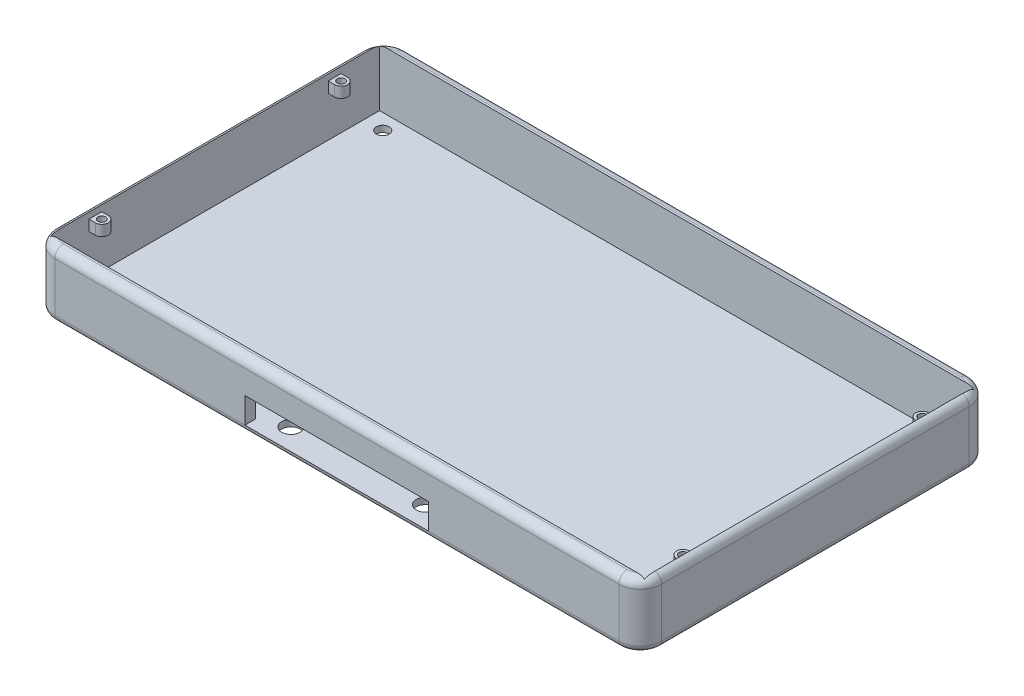
SolidWorks part; units mm, degrees
ref_plane "前视基准面" through (0, 0, 0) normal (0, 0, 1) x (1, 0, 0)
ref_plane "上视基准面" through (0, 0, 0) normal (0, 1, 0) x (1, 0, 0)
ref_plane "右视基准面" through (0, 0, 0) normal (1, 0, 0) x (0, 0, -1)
sketch "草图1" plane through (0, 0, 0) normal (0, 1, 0) x (1, 0, 0)
  line L1 (0, 0) -> (142, 0)
  line L2 (0, 0) -> (0, -82)
  line L3 (0, -82) -> (142, -82)
  line L4 (142, 0) -> (142, -82)
  dimension "D1" = 142
  dimension "D2" = 82
extrude "凸台-拉伸1" add sketch "草图1" along normal blind 15 contours L1 L4 L3 L2
shell "抽壳1" thickness 1.5 removed face at (71, 15, 41)
sketch "草图2" plane through (0, 1.5, 0) normal (0, 1, 0) x (1, 0, 0)
  line L0 (55.25, -77) -> (1.5, -77) construction
  line L1 (1.5, -1.5) -> (1.5, -80.5) construction
  line L2 (86.75, -77) -> (140.5, -77) construction
  line L3 (140.5, -1.5) -> (140.5, -80.5) construction
  line L4 (0, -82) -> (142, -82) construction
  circle A0 centre (86.75, -77) radius 2.15
  circle A1 centre (55.25, -77) radius 2.15
  dimension "D1" = 4.3
  dimension "D2" = 31.5
  dimension "5" = 5
extrude "切除-拉伸1" cut sketch "草图2" against normal blind 15
sketch "草图4" plane through (0, 1.5, 0) normal (0, 1, 0) x (1, 0, 0)
  line L0 (5.9, -75.85) -> (1.5, -75.85) construction
  line L1 (1.5, -1.5) -> (1.5, -80.5) construction
  line L2 (5.9, -75.85) -> (5.9, -1.5) construction
  line L3 (1.5, -1.5) -> (140.5, -1.5) construction
  line L4 (5.9, -6.15) -> (1.5, -6.15) construction
  line L5 (1.5, -1.5) -> (1.5, -80.5) construction
  line L6 (136.1, -75.85) -> (136.1, -1.5) construction
  line L7 (1.5, -1.5) -> (140.5, -1.5) construction
  line L8 (5.9, -6.15) -> (5.9, -80.5) construction
  line L9 (1.5, -80.5) -> (140.5, -80.5) construction
  line L10 (136.1, -6.15) -> (136.1, -80.5) construction
  line L11 (136.1, -75.85) -> (140.5, -75.85) construction
  line L12 (140.5, -1.5) -> (140.5, -80.5) construction
  line L13 (136.1, -6.15) -> (140.5, -6.15) construction
  circle A0 centre (5.9, -75.85) radius 1.5
  circle A1 centre (136.1, -75.85) radius 1.5
  circle A2 centre (5.9, -6.15) radius 1.5
  circle A3 centre (136.1, -6.15) radius 1.5
  dimension "D1" = 3
  dimension "D2" = 130.2
  dimension "D3" = 69.7
extrude "切除-拉伸2" cut sketch "草图4" against normal blind 15
sketch "草图5" plane through (0, 0, 82) normal (0, 0, 1) x (1, 0, 0)
  line L0 (0, 0) -> (142, 0) construction
  line L1 (49.5, 7.5) -> (92.5, 7.5)
  line L2 (49.5, 7.5) -> (49.5, 1.5)
  line L3 (49.5, 1.5) -> (92.5, 1.5)
  line L4 (92.5, 7.5) -> (92.5, 1.5)
  line L5 (49.5, 4.5) -> (0, 4.5) construction
  line L6 (0, 15) -> (0, 0) construction
  line L7 (92.5, 4.5) -> (142, 4.5) construction
  line L8 (142, 15) -> (142, 0) construction
  dimension "D1" = 43
  dimension "D2" = 6
  dimension "D3" = 1.5
extrude "切除-拉伸3" cut sketch "草图5" against normal blind 15
ref_plane "基准面4" through (0, 11, 0) normal (0, 1, 0) x (1, 0, 0)
sketch "草图6" plane through (0, 11, 0) normal (0, 1, 0) x (1, 0, 0)
  line L0 (1.5, -67.5) -> (4.5, -67.5)
  line L1 (1.5, -11.5) -> (4.5, -11.5)
  line L2 (1.5, -11.5) -> (1.5, -14.5)
  line L3 (1.5, -14.5) -> (4.5, -14.5)
  line L4 (4.5, -11.5) -> (4.5, -14.5)
  line L5 (1.5, -67.5) -> (1.5, -70.5)
  line L6 (1.5, -70.5) -> (4.5, -70.5)
  line L7 (4.5, -67.5) -> (4.5, -70.5)
  line L8 (137.5, -11.5) -> (140.5, -11.5)
  line L9 (137.5, -11.5) -> (137.5, -14.5)
  line L10 (137.5, -14.5) -> (140.5, -14.5)
  line L11 (140.5, -11.5) -> (140.5, -14.5)
  line L12 (137.5, -67.5) -> (140.5, -67.5)
  line L13 (137.5, -67.5) -> (137.5, -70.5)
  line L14 (137.5, -70.5) -> (140.5, -70.5)
  line L15 (140.5, -67.5) -> (140.5, -70.5)
  line L16 (140.5, -1.5) -> (140.5, -80.5) construction
  line L18 (1.5, -1.5) -> (1.5, -80.5) construction
  line L19 (1.5, -1.5) -> (140.5, -1.5) construction
  line L20 (1.5, -80.5) -> (49.5, -80.5) construction
  dimension "D1" = 3
  dimension "D2" = 3
  dimension "D3" = 3
  dimension "D4" = 0
  dimension "D5" = 3
  dimension "D6" = 0
  dimension "D7" = 10
  dimension "D8" = 10
  dimension "D9" = 3
extrude "凸台-拉伸2" add sketch "草图6" along normal blind 2.5
sketch "草图7" plane through (0, 13.5, 0) normal (0, 1, 0) x (1, 0, 0)
  line L0 (4.5, -11.5) -> (1.5, -11.5) construction
  line L1 (1.5, -11.5) -> (1.5, -14.5) construction
  line L2 (1.5, -70.5) -> (4.5, -70.5) construction
  line L3 (140.5, -1.5) -> (140.5, -80.5) construction
  line L4 (1.5, -1.5) -> (140.5, -1.5) construction
  line L5 (92.5, -80.5) -> (140.5, -80.5) construction
  circle A0 centre (3, -13) radius 0.9
  circle A1 centre (3, -69) radius 0.9024
  circle A2 centre (139, -69) radius 0.9
  circle A3 centre (139, -13) radius 0.9
  dimension "D1" = 1.8
  dimension "D5" = 1.8048
  dimension "D7" = 1.8
  dimension "D8" = 1.8
  dimension "D2" = 1.5
  dimension "D3" = 1.5
  dimension "D4" = 1.5
  dimension "D6" = 1.5
  dimension "D9" = 11.5
  dimension "D10" = 11.5
extrude "切除-拉伸4" cut sketch "草图7" against normal up to next
fillet "圆角4" 2 edges at (4.5, 12.25, 14.5) (4.5, 12.25, 11.5) type full round first side face at (3, 12.25, 14.5) second side face at (3, 12.25, 11.5) middle face at (4.5, 12.25, 13)
fillet "圆角5" 2 edges at (4.5, 12.25, 67.5) (4.5, 12.25, 70.5) type full round first side face at (3, 12.25, 67.5) second side face at (3, 12.25, 70.5) middle face at (4.5, 12.25, 69)
fillet "圆角6" 2 edges at (137.5, 12.25, 11.5) (137.5, 12.25, 14.5) type full round first side face at (139, 12.25, 11.5) second side face at (139, 12.25, 14.5) middle face at (137.5, 12.25, 13)
fillet "圆角7" 2 edges at (137.5, 12.25, 67.5) (137.5, 12.25, 70.5) type full round first side face at (139, 12.25, 67.5) second side face at (139, 12.25, 70.5) middle face at (137.5, 12.25, 69)
fillet "圆角8" radius 5 4 edges at (0, 7.5, 82) (0, 7.5, 0) (142, 7.5, 0) (142, 7.5, 82)
fillet "圆角13" radius 1.5 8 edges at (1.4645, 0, 1.4645) (71, 0, 0) (140.5355, 0, 1.4645) (142, 0, 41) (140.5355, 0, 80.5355) (71, 0, 82) (1.4645, 0, 80.5355) (0, 0, 41)
sketch "草图8" plane through (0, 15, 0) normal (0, 1, 0) x (1, 0, 0)
  line L0 (1.5, -1.5) -> (140.5, -1.5) construction
  line L1 (1.5, -1.5) -> (140.5, -1.5)
  line L2 (1.5, -1.5) -> (1.5, -2.5)
  line L3 (1.5, -2.5) -> (140.5, -2.5)
  line L4 (140.5, -1.5) -> (140.5, -2.5)
  line L5 (1.5, -1.5) -> (1.5, -80.5) construction
  line L6 (140.5, -1.5) -> (140.5, -80.5) construction
  dimension "D1" = 1
  dimension "D2" = 0
  dimension "D3" = 0
  dimension "D4" = 0
extrude "凸台-拉伸7" add sketch "草图8" against normal up to surface (13.5 mm away) up to face at (71, 1.5, 61.125)
sketch "草图9" plane through (0, 15, 0) normal (0, 1, 0) x (1, 0, 0)
  line L0 (49.5, -80.5) -> (49.5, -82) construction
  line L1 (49.5, -79.5) -> (92.5, -79.5)
  line L2 (49.5, -79.5) -> (49.5, -80.5)
  line L3 (49.5, -80.5) -> (92.5, -80.5)
  line L4 (92.5, -79.5) -> (92.5, -80.5)
  line L5 (92.5, -80.5) -> (92.5, -82) construction
  line L6 (1.5, -80.5) -> (140.5, -80.5) construction
  dimension "D1" = 1
  dimension "D2" = 0
  dimension "D3" = 0
  dimension "D4" = 0
extrude "凸台-拉伸8" add sketch "草图9" against normal up to surface (7.5 mm away) up to face at (71, 7.5, 81.25)
sketch "草图10" plane through (0, 15, 0) normal (0, 1, 0) x (1, 0, 0)
  line L0 (140.5, -2.5) -> (140.5, -80.5) construction
  line L1 (1.5, -80.5) -> (49.5, -80.5)
  line L2 (1.5, -80.5) -> (1.5, -79.5)
  line L3 (1.5, -79.5) -> (49.5, -79.5)
  line L4 (49.5, -80.5) -> (49.5, -79.5)
  line L5 (92.5, -80.5) -> (140.5, -80.5)
  line L6 (92.5, -80.5) -> (92.5, -79.5)
  line L7 (92.5, -79.5) -> (140.5, -79.5)
  line L8 (140.5, -80.5) -> (140.5, -79.5)
extrude "凸台-拉伸9" add sketch "草图10" against normal up to surface (13.5 mm away) up to face at (71, 1.5, 61.375)
fillet "圆角14" radius 2 8 edges at (1.4645, 15, 80.5355) (0, 15, 41) (1.4645, 15, 1.4645) (71, 15, 0) (140.5355, 15, 1.4645) (142, 15, 41) (140.5355, 15, 80.5355) (71, 15, 82)
